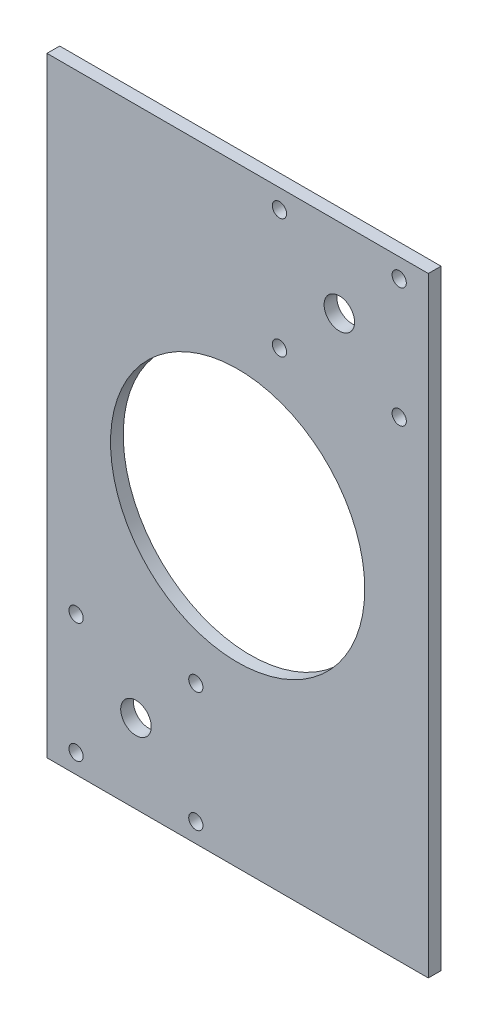
SolidWorks part; units mm, degrees
material "Plain Carbon Steel"
ref_plane "Front Plane" through (0, 0, 0) normal (0, 0, 1) x (1, 0, 0)
ref_plane "Top Plane" through (0, 0, 0) normal (0, 1, 0) x (1, 0, 0)
ref_plane "Right Plane" through (0, 0, 0) normal (1, 0, 0) x (0, 0, -1)
sketch "Sketch1" plane through (0, 0, 0) normal (0, 0, 1) x (1, 0, 0)
  line L1 (-75, -120) -> (75, -120)
  line L2 (-75, -120) -> (-75, 120)
  line L3 (-75, 120) -> (75, 120)
  line L4 (75, -120) -> (75, 120)
  line L5 (-75, -120) -> (75, 120) construction
  line L6 (-75, 120) -> (75, -120) construction
  point P0 (0, 0)
  dimension "D1" = 150
  dimension "D2" = 240
extrude "Boss-Extrude1" add sketch "Sketch1" along normal blind 5
sketch "Sketch2" [suppressed] plane through (0, 0, 0) normal (0, 0, -1) x (-1, 0, 0)
  line L0 (61, 200) -> (61, -200) construction
  line L1 (-61, 314.7216) -> (-204.3993, 314.7216)
  line L2 (-61, 314.7216) -> (-61, -251.9618)
  line L3 (-61, -251.9618) -> (-204.3993, -251.9618)
  line L4 (-204.3993, 314.7216) -> (-204.3993, -251.9618)
  line L6 (61, 279.3211) -> (244.4765, 279.3211)
  line L7 (61, 279.3211) -> (61, -295.1839)
  line L8 (61, -295.1839) -> (244.4765, -295.1839)
  line L9 (244.4765, 279.3211) -> (244.4765, -295.1839)
  line L10 (-61, -200) -> (-61, -140) construction
extrude "Cut-Extrude1" [suppressed] cut sketch "Sketch2" against normal through all
sketch "Sketch3" [suppressed] plane through (49, 0, 0) normal (1, 0, 0) x (0, 0, -1)
  circle A0 centre (-6.722, 55.3681) radius 5.3835
surface "Surface-Extrude1" [suppressed] sketch "Sketch3"
sketch "Sketch4" [suppressed] plane through (-49, 0, 0) normal (-1, 0, 0) x (0, 0, 1)
  line L1 (2, 80) -> (0, 80) construction
  line L2 (0, -80) -> (0, 80) construction
  point P0 (7.5, 76)
  dimension "D1" = 4
  dimension "D2" = 7.5
ref_axis "Axis1" [suppressed] through (-49, 76, 7.5) along (1, 0, 0)
sketch "Sketch5" [suppressed] plane through (0, 0, 0) normal (0, 0, -1) x (-1, 0, 0)
  line L0 (49, 80) -> (49, -80) construction
  line L1 (-49, 80) -> (49, 80)
  line L2 (-49, 80) -> (-49, 60.2594)
  line L3 (-49, 60.2594) -> (49, 60.2594)
  line L4 (49, 80) -> (49, 60.2594)
extrude "Cut-Extrude2" [suppressed] cut sketch "Sketch5" against normal blind 3
sketch "Sketch6" [suppressed] plane through (0, 0, 2) normal (0, 0, 1) x (1, 0, 0)
  line L0 (0, 0) -> (103.2002, 0) construction
  line L1 (0, 82.0129) -> (0, 105.8319) construction
  line L2 (0, 82.0129) -> (-20.8963, 82.0129) construction
  circle A0 centre (0, 82.0129) radius 5
  circle A1 centre (0, -82.0129) radius 5
  circle A2 centre (-11.3212, 93.334) radius 1.5
  circle A3 centre (-11.3212, 70.6917) radius 1.5
  circle A4 centre (11.3212, 70.6917) radius 1.5
  circle A5 centre (11.3212, 93.334) radius 1.5
  circle A6 centre (-11.3212, -70.6917) radius 1.5
  circle A7 centre (11.3212, -70.6917) radius 1.5
  circle A8 centre (11.3212, -93.334) radius 1.5
  circle A9 centre (-11.3212, -93.334) radius 1.5
  dimension "D1" = 10
  dimension "D3" = 3
  dimension "D2" = 164.0257
extrude "Cut-Extrude3" [suppressed] cut sketch "Sketch6" against normal through all
sketch "Sketch7" plane through (0, 0, 5) normal (0, 0, 1) x (1, 0, 0)
  line L0 (0, 0) -> (0, 68.4211) construction
  line L1 (44.1624, 0) -> (-44.1624, 0) construction
  line L2 (40, 88.9) -> (-40, -88.9) construction
  line L3 (0, 0) -> (-0.1689, 0.076) construction
  circle A0 centre (-63.55, -112.45) radius 2.8 construction
  circle A1 centre (-63.55, -65.35) radius 2.8 construction
  circle A2 centre (-16.45, -65.35) radius 2.8 construction
  circle A3 centre (-16.45, -112.45) radius 2.8 construction
  circle A4 centre (-63.55, -112.45) radius 2.8
  circle A5 centre (-63.55, -65.35) radius 2.8
  circle A6 centre (-16.45, -65.35) radius 2.8
  circle A7 centre (-16.45, -112.45) radius 2.8
  circle A8 centre (-16.45, 112.45) radius 2.8
  circle A9 centre (-16.45, 65.35) radius 2.8
  circle A10 centre (-63.55, 65.35) radius 2.8
  circle A11 centre (-63.55, 112.45) radius 2.8
  circle A12 centre (63.55, 112.45) radius 2.8
  circle A13 centre (63.55, 65.35) radius 2.8
  circle A14 centre (16.45, 65.35) radius 2.8
  circle A15 centre (16.45, 112.45) radius 2.8
  circle A16 centre (16.45, -112.45) radius 2.8
  circle A17 centre (16.45, -65.35) radius 2.8
  circle A18 centre (63.55, -65.35) radius 2.8
  circle A19 centre (63.55, -112.45) radius 2.8
  circle A20 centre (-40, -88.9) radius 6
  circle A21 centre (-40, 88.9) radius 6
  circle A22 centre (40, 88.9) radius 6
  circle A23 centre (40, -88.9) radius 6
  circle A24 centre (0, 0) radius 97.4844 construction
  dimension "D1" = 12
extrude "Cut-Extrude4" cut sketch "Sketch7" against normal through all
sketch "Sketch8" plane through (0, 0, 5) normal (0, 0, 1) x (1, 0, 0)
  circle A0 centre (0, 0) radius 50
  dimension "D1" = 100
extrude "Cut-Extrude5" cut sketch "Sketch8" against normal through all
other "DeleteFace1" face at (-66.35, 112.45, 0) face at (-66.35, 65.35, 0) face at (-19.25, 65.35, 0) face at (-19.25, 112.45, 0) face at (-46, 88.9, 0) face at (13.65, -112.45, 0) face at (34, -88.9, 0) face at (13.65, -65.35, 0) face at (60.75, -65.35, 0) face at (60.75, -112.45, 0) and patch yes
ref_axis "Axis2" through (0, 0, 5) along (0, 0, 1)
